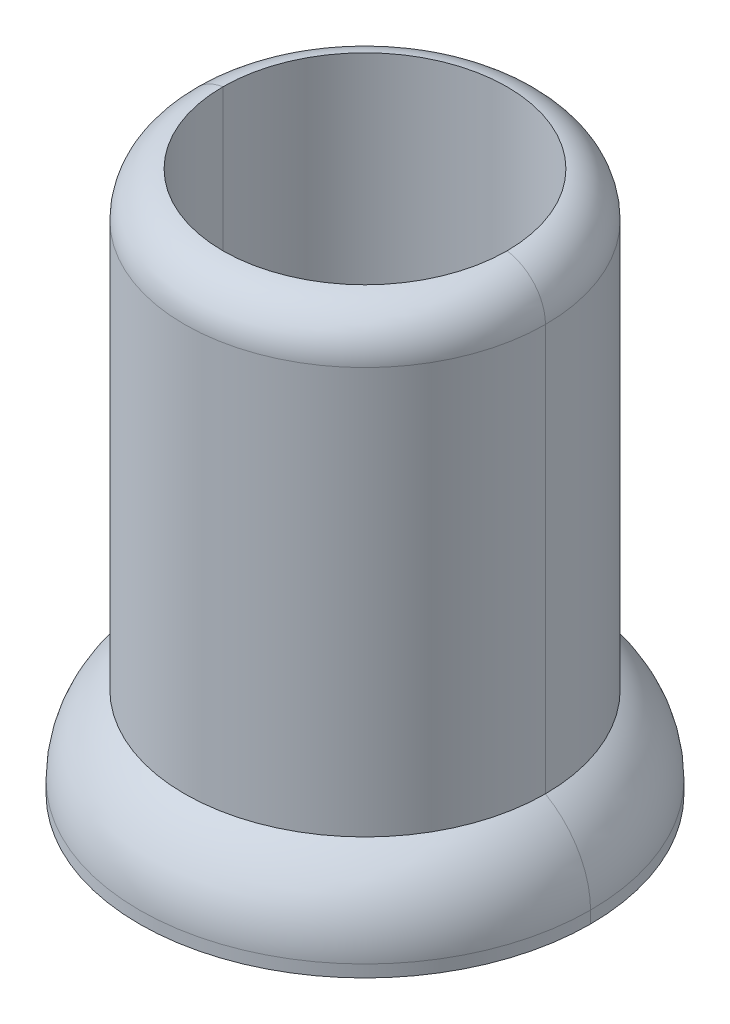
SolidWorks part; units mm, degrees
ref_plane "Front Plane" through (0, 0, 0) normal (0, 0, 1) x (1, 0, 0)
ref_plane "Top Plane" through (0, 0, 0) normal (0, 1, 0) x (1, 0, 0)
ref_plane "Right Plane" through (0, 0, 0) normal (1, 0, 0) x (0, 0, -1)
sketch "Sketch1" plane through (0, 0, 0) normal (0, 1, 0) x (1, 0, 0)
  circle A0 centre (0, 0) radius 4
  dimension "D1" = 8
extrude "Boss-Extrude1" add sketch "Sketch1" along normal blind 10
sketch "Sketch6" plane through (0, 0, 0) normal (0, -1, 0) x (1, 0, 0)
  circle A0 centre (0, 0) radius 5
  dimension "D1" = 10
extrude "Boss-Extrude2" add sketch "Sketch6" along normal blind 2
sketch "Sketch8" plane through (0, 10, 0) normal (0, 1, 0) x (1, 0, 0)
  circle A0 centre (0, 0) radius 3.15
  dimension "D1" = 6.3
extrude "Cut-Extrude2" cut sketch "Sketch8" against normal through all
fillet "Fillet1" radius 2 1 edges at (0, 0, -5)
fillet "Fillet2" radius 1 1 edges at (0, 10, 4)
ref_plane "Plane1" through (0, 10, 0) normal (0, -1, 0) x (-1, 0, 0)
sketch "Sketch10" plane through (0, 10, 0) normal (0, -1, 0) x (-1, 0, 0)
  line L0 (-5, 0) -> (5, 0)
  circle A0 centre (0, 0) radius 5 construction
split "Split2" trim tools "Sketch10" bodies to split 104 resulting bodies 107 108
